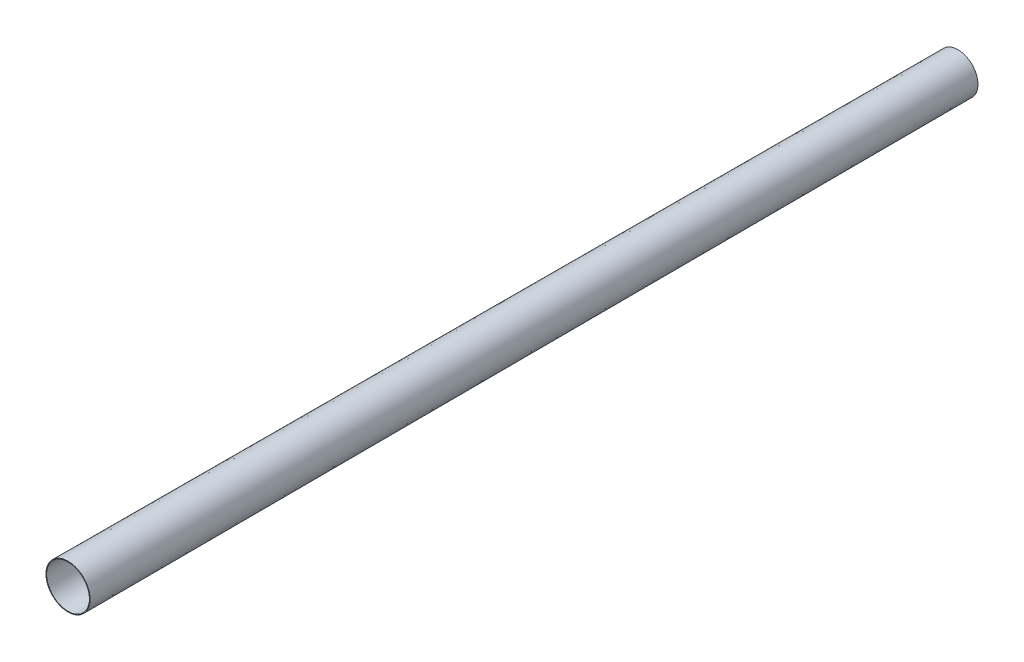
SolidWorks part; units mm, degrees
ref_plane "Front Plane" through (0, 0, 0) normal (0, 0, 1) x (1, 0, 0)
ref_plane "Top Plane" through (0, 0, 0) normal (0, 1, 0) x (1, 0, 0)
ref_plane "Right Plane" through (0, 0, 0) normal (1, 0, 0) x (0, 0, -1)
sketch "Sketch1" plane through (0, 0, 0) normal (0, 0, 1) x (1, 0, 0)
  circle A0 centre (0, 0) radius 15.3156
  circle A1 centre (0, 0) radius 15.8156
  dimension "D2" = 31.6312
  dimension "D1" = 0.5
ref_plane "Plane1" through (0, 0, 700.9946) normal (0, 0, 1) x (1, 0, 0)
sketch "Sketch2" plane through (0, 0, 700.9946) normal (0, 0, 1) x (1, 0, 0)
  circle A0 centre (0, 0) radius 17.3661
  circle A1 centre (0, 0) radius 16.8661
  dimension "D2" = 34.7323
  dimension "D1" = 0.5
loft "Loft1" add section "Sketch1" section "Sketch2" start constraint default connector at (-14.3061, -6.7429, 0) connector at (-15.7319, -7.3546, 700.9946)
shell "Shell1" thickness 0.5 removed face at (15.8156, 0, 0) removed face at (17.3661, 0, 700.9946)
